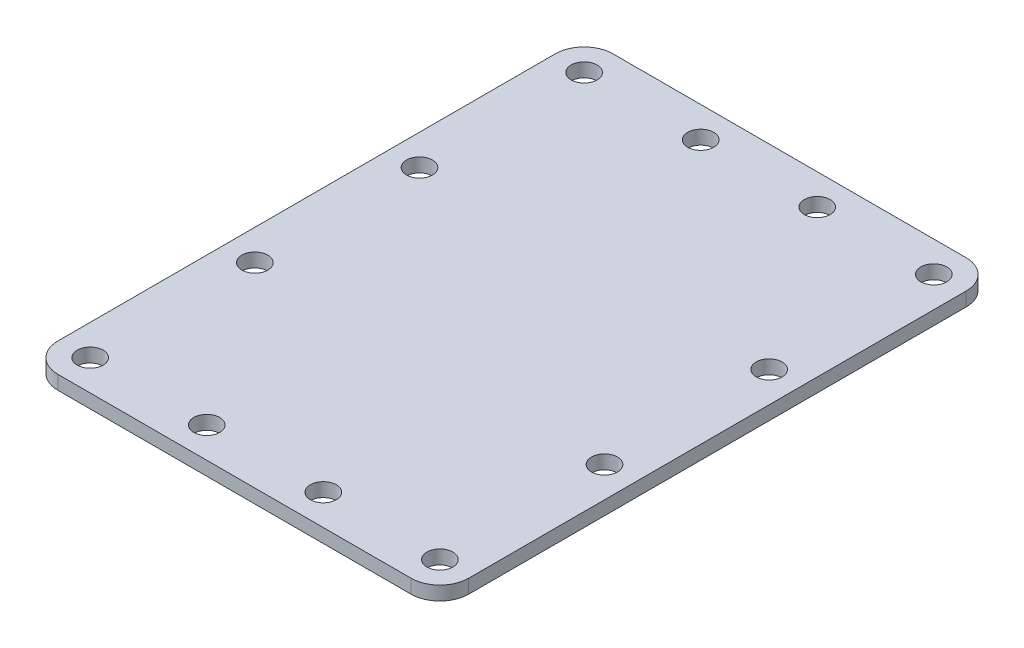
SolidWorks part; units mm, degrees
material "AISI 1020"
ref_plane "Plano frontal" through (0, 0, 0) normal (0, 0, 1) x (1, 0, 0)
ref_plane "Plano superior" through (0, 0, 0) normal (0, 1, 0) x (1, 0, 0)
ref_plane "Plano direito" through (0, 0, 0) normal (1, 0, 0) x (0, 0, -1)
sketch "Esboço1" plane through (0, 0, 0) normal (0, 1, 0) x (1, 0, 0)
  line L0 (-60.6, 85.6) -> (-20.2, 85.6) construction
  line L1 (-61.2, -96.2) -> (61.2, -96.2)
  line L2 (-71.2, -86.2) -> (-71.2, 86.2)
  line L3 (-61.2, 96.2) -> (61.2, 96.2)
  line L4 (71.2, -86.2) -> (71.2, 86.2)
  line L5 (-71.2, -96.2) -> (71.2, 96.2) construction
  line L6 (-71.2, 96.2) -> (71.2, -96.2) construction
  line L7 (-60.6, -85.6) -> (60.6, -85.6) construction
  line L8 (-60.6, -85.6) -> (-60.6, 85.6) construction
  line L11 (60.6, -28.5333) -> (60.6, 28.5333) construction
  line L12 (-55, 0) -> (55, 0) construction
  line L13 (-20.2, 85.6) -> (20.2, 85.6) construction
  line L14 (20.2, 85.6) -> (60.6, 85.6) construction
  line L15 (60.6, 85.6) -> (60.6, 28.5333) construction
  line L18 (60.6, -28.5333) -> (60.6, -85.6) construction
  line L19 (0, -85.6) -> (0, 85.6) construction
  line L20 (1.2763, 0) -> (60.6, 0) construction
  arc A0 (-61.2, 96.2) -> (-71.2, 86.2) centre (-61.2, 86.2) ccw
  arc A1 (-71.2, -86.2) -> (-61.2, -96.2) centre (-61.2, -86.2) ccw
  arc A2 (61.2, -96.2) -> (71.2, -86.2) centre (61.2, -86.2) ccw
  arc A3 (71.2, 86.2) -> (61.2, 96.2) centre (61.2, 86.2) ccw
  circle A6 centre (-60.6, 85.6) radius 4.5
  circle A7 centre (60.6, 85.6) radius 4.5
  circle A8 centre (-60.6, -85.6) radius 4.5
  circle A9 centre (60.6, -85.6) radius 4.5
  circle A10 centre (-20.2, 85.6) radius 4.5
  circle A11 centre (20.2, 85.6) radius 4.5
  circle A12 centre (60.6, 28.5333) radius 4.5
  circle A14 centre (60.6, -28.5333) radius 4.5
  circle A17 centre (20.2, -85.6) radius 4.5
  circle A18 centre (-20.2, -85.6) radius 4.5
  circle A19 centre (-60.6, -28.5333) radius 4.5
  circle A20 centre (-60.6, 28.5333) radius 4.5
  point P0 (0, 0)
  point P18 (16.7054, -22.5711)
  point P34 (61.8763, 0)
  point P40 (0, 0)
  point P42 (0, 0)
  dimension "D3" = 10
  dimension "D6" = 9
  dimension "D1" = 192.4
  dimension "D2" = 142.4
  dimension "D4" = 121.2
  dimension "D5" = 171.2
base flange "Flange-base1" sketch "Esboço1" thickness 4.8 reverse thickness direction no parameters "D1"=0.7366
sketch "Curva-Linhas1" [suppressed] plane through (0, 0, 0) normal (0, 1, 0) x (1, 0, 0)
sketch "Caixa delimitadora1" [suppressed] plane through (0, 0, 0) normal (0, 1, 0) x (1, 0, 0)
sheet metal parameters "Chapa metálica1" thickness 4.8 parameters "D1"=0.7366
flat pattern "Padrão-Plano1" [suppressed]
sketch "Curva-Linhas2" plane through (0, 0, 0) normal (0, 1, 0) x (1, 0, 0)
sketch3d "Caixa delimitadora2" [suppressed]
  line L0 (-10, 10, 0) -> (-10, -182.4, 0) construction
  line L1 (132.4, 10, 0) -> (132.4, -182.4, 0) construction
  line L2 (-10, 10, 0) -> (132.4, 10, 0) construction
  line L3 (-10, -182.4, 0) -> (132.4, -182.4, 0) construction
